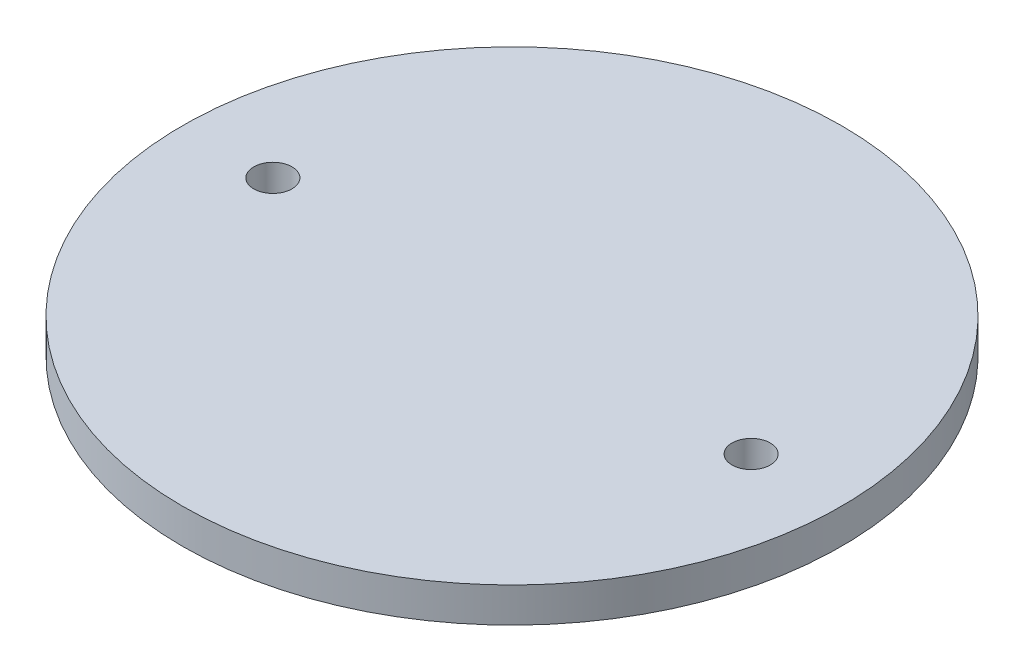
SolidWorks part; units mm, degrees
material "Balsa"
ref_plane "Front Plane" through (0, 0, 0) normal (0, 0, 1) x (1, 0, 0)
ref_plane "Top Plane" through (0, 0, 0) normal (0, 1, 0) x (1, 0, 0)
ref_plane "Right Plane" through (0, 0, 0) normal (1, 0, 0) x (0, 0, -1)
sketch "Sketch1" plane through (0, 0, 0) normal (0, 1, 0) x (1, 0, 0)
  line L0 (-37.9, 0) -> (37.9, 0) construction
  line L1 (0, 37.9) -> (0, -37.9) construction
  circle A0 centre (0, 0) radius 37.9
  circle A1 centre (-27.5, 0) radius 2.2
  circle A2 centre (27.5, 0) radius 2.2
  dimension "D1" = 55
  dimension "D2" = 75.8
  dimension "D3" = 4.4
extrude "Boss-Extrude1" add sketch "Sketch1" along normal blind 4
